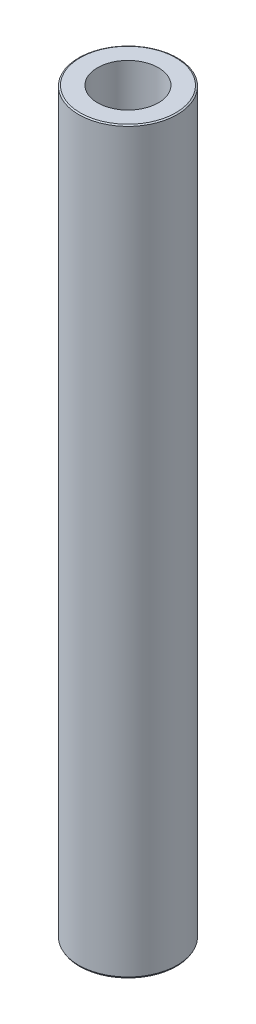
SolidWorks part; units mm, degrees
ref_plane "Front Plane" through (0, 0, 0) normal (0, 0, 1) x (1, 0, 0)
ref_plane "Top Plane" through (0, 0, 0) normal (0, 1, 0) x (1, 0, 0)
ref_plane "Right Plane" through (0, 0, 0) normal (1, 0, 0) x (0, 0, -1)
sketch "Sketch1" plane through (0, 0, 0) normal (0, 1, 0) x (1, 0, 0)
  circle A0 centre (0, 0) radius 22.5
  dimension "SHAFT_OD" = 45
extrude "Boss-Extrude1" add sketch "Sketch1" along normal blind 337.7052
sketch "Sketch2" plane through (0, 0, 0) normal (0, 1, 0) x (1, 0, 0)
  circle A0 centre (0, 0) radius 13.9181
  dimension "BORE_D" = 27.8363
extrude "Cut-Extrude1" cut sketch "Sketch2" along normal through all
chamfer "Chamfer1" distance 0.3756 angle 60.65 2 edges at (0, 337.7052, 22.5) (0, 0, 22.5) first distance on face at (0, 337.7052, 22.5) first distance on face at (0, 0, 13.9181)
